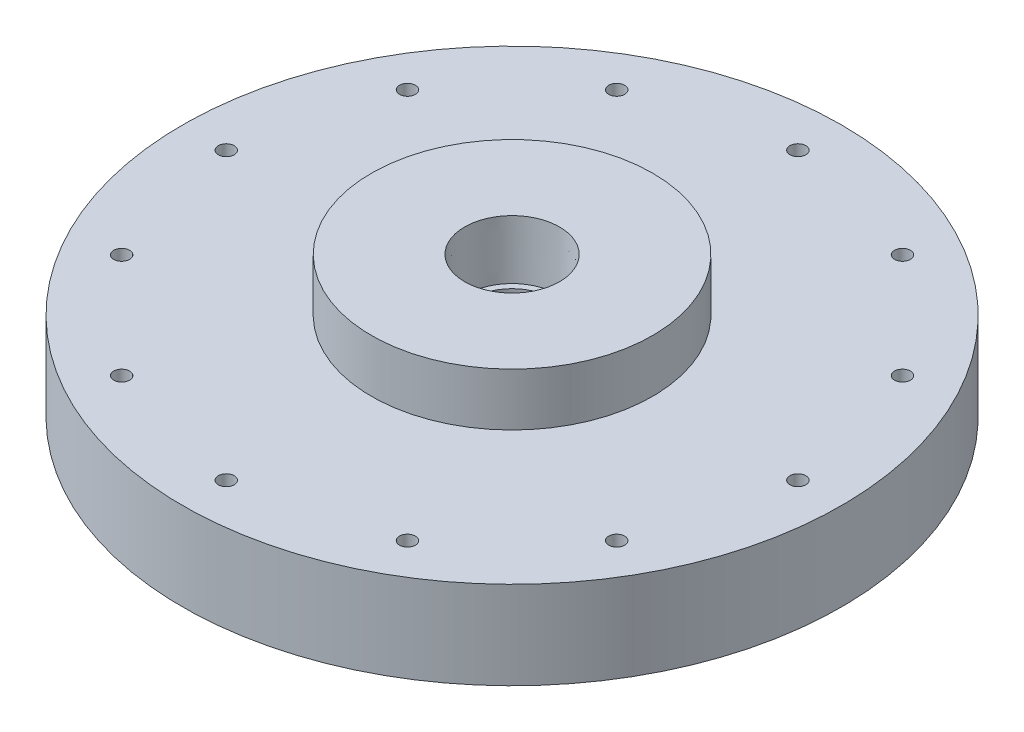
SolidWorks part; units mm, degrees
material "7075-T6 (SN)"
ref_plane "Front Plane" through (0, 0, 0) normal (0, 0, 1) x (1, 0, 0)
ref_plane "Top Plane" through (0, 0, 0) normal (0, 1, 0) x (1, 0, 0)
ref_plane "Right Plane" through (0, 0, 0) normal (1, 0, 0) x (0, 0, -1)
sketch "Sketch2" plane through (0, 0, 0) normal (0, 1, 0) x (1, 0, 0)
  circle A1 centre (0, 0) radius 25.4
  dimension "D1" = 50.8
extrude "Base Cylinder" add sketch "Sketch2" along normal blind 19.05
sketch "Sketch3" plane through (0, 0, 0) normal (0, -1, 0) x (1, 0, 0)
  circle A1 centre (0, 0) radius 59.5312
  dimension "D1" = 119.0625
extrude "Aft Flange" add sketch "Sketch3" against normal blind 9.525
sketch "Sketch For Bolt Holes" plane through (0, 0, 0) normal (0, -1, 0) x (1, 0, 0)
  circle A0 centre (-51.6255, 0) radius 1.5875
  circle A1 centre (-44.709, 25.8128) radius 1.5875
  circle A2 centre (-25.8128, 44.709) radius 1.5875
  circle A3 centre (0, 51.6255) radius 1.5875
  circle A4 centre (25.8127, 44.709) radius 1.5875
  circle A5 centre (44.709, 25.8128) radius 1.5875
  circle A6 centre (51.6255, 0) radius 1.5875
  circle A7 centre (44.709, -25.8127) radius 1.5875
  circle A8 centre (25.8128, -44.709) radius 1.5875
  circle A9 centre (0, -51.6255) radius 1.5875
  circle A10 centre (-25.8127, -44.709) radius 1.5875
  circle A11 centre (-44.709, -25.8128) radius 1.5875
  point P36 (0, 0)
  dimension "D2" = 3.175
  dimension "D1" = 51.6255
  dimension "D3" = 12
hole_wizard "Bolt Circle" positions "Sketch8" profile "Sketch9" hole size "#4-40" standard "ANSI Inch" end condition up to next
sketch "Sketch8" plane through (0, 0, 0) normal (0, -1, 0) x (-1, 0, 0)
  point P0 (-25.8127, -44.709)
  point P3 (-44.709, -25.8128)
  point P6 (-51.6255, 0)
  point P9 (-44.709, 25.8127)
  point P12 (-25.8128, 44.709)
  point P15 (0, 51.6255)
  point P18 (25.8127, 44.709)
  point P21 (44.709, 25.8128)
  point P24 (51.6255, 0)
  point P27 (44.709, -25.8128)
  point P30 (25.8128, -44.709)
  point P33 (0, -51.6255)
  point P36 (-25.8127, -44.709)
  point P38 (-44.709, -25.8128)
  point P40 (-51.6255, 0)
sketch "Sketch9" plane through (25.8127, 0, 44.709) normal (1, 0, 0) x (0, 0, -1)
  line L0 (0, 0) -> (0, 9.525)
  line L1 (0, 9.525) -> (1.4351, 9.525)
  line L2 (1.4351, 9.525) -> (1.4351, 0)
  line L5 (1.4351, 0) -> (0, 0)
  line L11 (0, -6.35) -> (0, 107.95) construction
  dimension "Thru Hole Dia." = 2.8702
  dimension "Thru Hole Depth" = 9.525
sketch "Dowel Hole Sketch" plane through (0, 0, 0) normal (0, -1, 0) x (1, 0, 0)
  line L0 (0, 0) -> (-51.6255, 0) construction
  line L1 (0, 0) -> (-49.8664, -13.3617) construction
  line L2 (0, 0) -> (0, -51.6255) construction
  line L3 (0, 0) -> (49.8664, 13.3617) construction
  circle A0 centre (0, 0) radius 51.6255
  circle A1 centre (-49.8664, -13.3617) radius 4.6172
  circle A2 centre (49.8664, 13.3617) radius 3.4532
  dimension "D1" = 15
ref_plane "Hoop Mid-Plane" through (0, 190.5, 0) normal (0, 1, 0) x (1, 0, 0)
sketch "Sketch15" plane through (0, 19.05, 0) normal (0, 1, 0) x (1, 0, 0)
  circle A0 centre (0, 0) radius 7.1106
hole_wizard "3/8 NPT Tapped Hole1" positions "Sketch16" profile "Sketch17" size "3/8" standard "ANSI Inch"
sketch "Sketch16" plane through (0, 19.05, 0) normal (0, 1, 0) x (1, 0, 0)
  point P0 (0, 0)
sketch "Sketch17" plane through (0, 19.05, 0) normal (1, 0, 0) x (0, 0, 1)
  line L0 (0, 0) -> (0, 21.8146)
  line L1 (7.1374, 17.526) -> (0, 21.8146)
  line L2 (-7.1374, 17.526) -> (0, 21.8146) construction
  line L3 (7.1374, 17.526) -> (7.1374, 10.414)
  line L4 (7.1374, 10.414) -> (8.2632, 10.414)
  line L5 (8.2632, 10.414) -> (8.575, 0)
  line L6 (-8.2632, 10.414) -> (-8.575, 0) construction
  line L7 (8.575, 0) -> (0, 0)
  line L8 (0, -6.35) -> (0, 107.95) construction
  line L11 (-7.1374, 10.414) -> (-8.2632, 10.414) construction
  dimension "Tap Drill Dia." = 14.2748
  dimension "Tap Drill Depth" = 17.526
  dimension "Thread Dia." = 17.15
  dimension "Thread Angle" = 3.43
  dimension "Thread Depth" = 10.414
  dimension "Drill Angle" = 118
sketch "Sketch18" plane through (0, 0, 0) normal (0, -1, 0) x (1, 0, 0)
  circle A0 centre (0, 0) radius 59.5312
extrude "Boss-Extrude1" add sketch "Sketch18" along normal blind 6.35
sketch "Sketch19" plane through (0, -6.35, 0) normal (0, -1, 0) x (1, 0, 0)
  circle A3 centre (0, 0) radius 56.3562
  dimension "D1" = 112.7125
extrude "Cut-Extrude1" cut sketch "Sketch19" against normal blind 6.35
